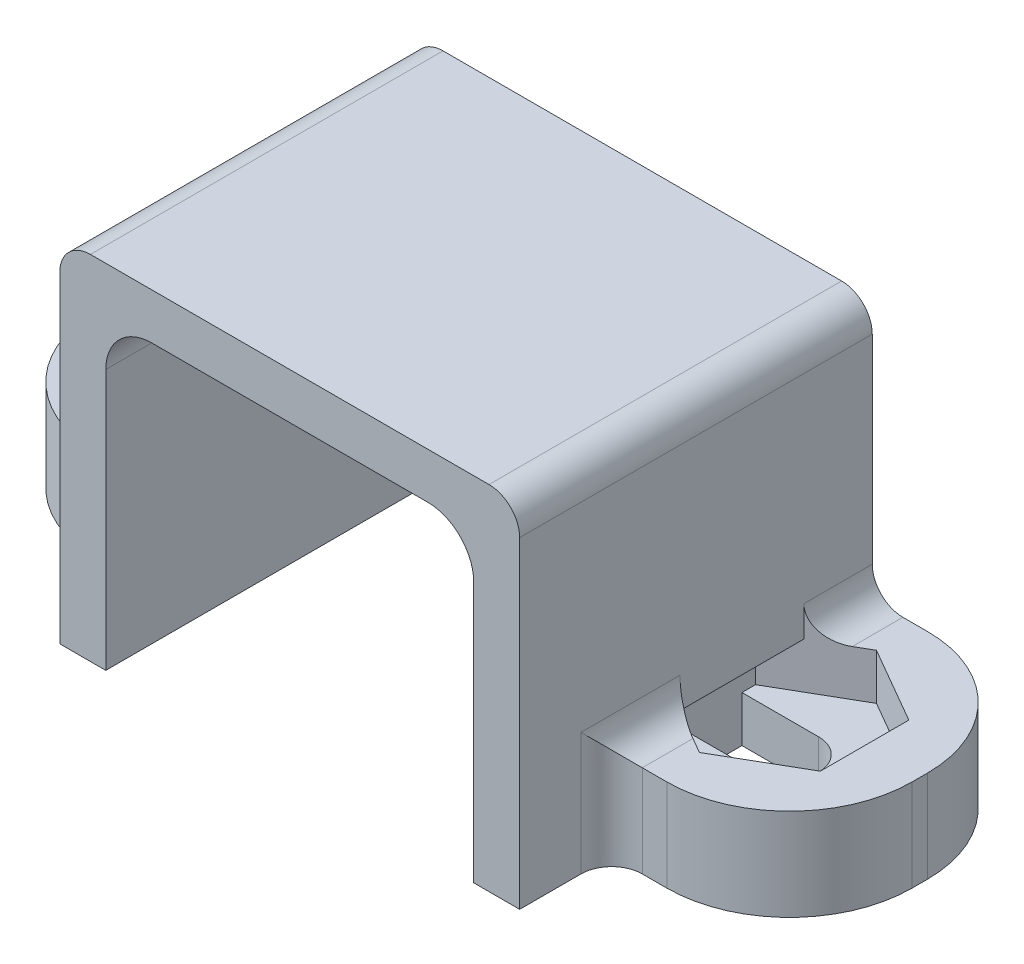
SolidWorks part; units mm, degrees
ref_plane "Front Plane" through (0, 0, 0) normal (0, 0, 1) x (1, 0, 0)
ref_plane "Top Plane" through (0, 0, 0) normal (0, 1, 0) x (1, 0, 0)
ref_plane "Right Plane" through (0, 0, 0) normal (1, 0, 0) x (0, 0, -1)
sketch "Sketch1" plane through (0, 0, 0) normal (0, 0, 1) x (1, 0, 0)
  line L0 (0, 0) -> (1.5, 0)
  line L1 (1.5, 0) -> (1.5, 10)
  line L2 (0, 0) -> (0, 10)
  line L3 (0, 10) -> (0, 11.5)
  line L4 (0, 11.5) -> (15, 11.5)
  line L5 (15, 11.5) -> (15, 0)
  line L6 (15, 0) -> (13.5, 0)
  line L7 (13.5, 0) -> (13.5, 10)
  line L8 (13.5, 10) -> (1.5, 10)
extrude "Boss-Extrude1" add sketch "Sketch1" along normal blind 17
sketch "Sketch12" plane through (0, 0, 0) normal (0, -1, 0) x (1, 0, 0)
  line L2 (15, 8) -> (0, 8)
  line L3 (15, 17) -> (15, 0) construction
  line L4 (0, 17) -> (0, 0) construction
split "Split2" trim tools "Sketch12" bodies to split 101 resulting bodies 116 117
combine bodies "Combine2" operation type add bodies to combine 116 117
sketch "Sketch13" plane through (0, 0, 0) normal (0, -1, 0) x (1, 0, 0)
  line L0 (7.5, 0) -> (7.5, 1.8013) construction
  line L1 (0, 0) -> (-5.8, 0)
  line L2 (0, 0) -> (0, 8.5)
  line L3 (0, 8.5) -> (-5.8, 8.5)
  line L4 (-5.8, 0) -> (-5.8, 8.5)
  line L5 (1.5, 0) -> (13.5, 0) construction
  line L6 (20.8, 0) -> (20.8, 8.5)
  line L7 (15, 8.5) -> (20.8, 8.5)
  line L8 (15, 0) -> (15, 8.5)
  line L9 (15, 0) -> (20.8, 0)
extrude "Boss-Extrude10" add sketch "Sketch13" against normal blind 3
fillet "Fillet7" radius 4 4 edges at (20.8, 1.5, 8.5) (20.8, 1.5, 0) (-5.8, 1.5, 0) (-5.8, 1.5, 8.5)
sketch "Sketch15" plane through (0, 0, 0) normal (-1, 0, 0) x (0, 0, 1)
  line L0 (0, 3) -> (17, 3)
  line L1 (17, 11.5) -> (17, 0) construction
split "Split3" trim tools "Sketch15" bodies to split 120 resulting bodies 121 122 123
sketch "Sketch16" plane through (0, 3, 0) normal (0, 1, 0) x (1, 0, 0)
  line L0 (1, -4.25) -> (-1.5, -4.25) construction
  line L2 (13.5, 0) -> (1.5, 0) construction
  line L3 (-1.5, -7.1368) -> (1, -5.6934)
  line L4 (1, -5.6934) -> (1, -2.8066)
  line L5 (1, -2.8066) -> (-1.5, -1.3632)
  line L6 (-1.5, -1.3632) -> (-4, -2.8066)
  line L7 (-4, -2.8066) -> (-4, -5.6934)
  line L8 (-4, -5.6934) -> (-1.5, -7.1368)
  line L9 (7.5, 0) -> (7.5, -2.8066) construction
  line L10 (7.5, -2.8066) -> (7.5, -4.25) construction
  line L11 (7.5, -4.25) -> (-1.5, -4.25) construction
  line L12 (-4, -2.8066) -> (-1.5, -1.3632)
  line L13 (-1.5, -7.1368) -> (-4, -5.6934)
  line L14 (1, -5.6934) -> (-1.5, -7.1368)
  line L15 (-1.5, -1.3632) -> (1, -2.8066)
  line L16 (14, -4.25) -> (16.5, -4.25) construction
  line L17 (16.5, -1.3632) -> (14, -2.8066)
  line L18 (14, -5.6934) -> (16.5, -7.1368)
  line L19 (16.5, -7.1368) -> (19, -5.6934)
  line L20 (19, -2.8066) -> (16.5, -1.3632)
  line L21 (19, -5.6934) -> (16.5, -7.1368)
  line L22 (19, -2.8066) -> (19, -5.6934)
  line L23 (16.5, -1.3632) -> (19, -2.8066)
  line L24 (14, -2.8066) -> (16.5, -1.3632)
  line L25 (14, -5.6934) -> (14, -2.8066)
  line L26 (16.5, -7.1368) -> (14, -5.6934)
extrude "Cut-Extrude1" cut sketch "Sketch16" against normal blind 1.5 contours L7 L8 L3 L4 L5 L6 | L25 L18 L19 L22 L20 L17 region at (-1.5, 3, 4.25) region at (16.5, 3, 4.25)
sketch "Sketch17" plane through (0, 1.5, 0) normal (0, 1, 0) x (1, 0, 0)
  line L0 (-1.5, -1.3632) -> (-1.5, -7.1368) construction
  line L3 (7.5, 0) -> (7.5, -1.3632) construction
  line L5 (16.5, -1.3632) -> (16.5, -7.1368) construction
  line L6 (16.5, -5.25) -> (14, -5.25)
  line L8 (16.5, -3.25) -> (14, -3.25)
  line L9 (14, -3.25) -> (14, -5.25)
  line L10 (1, -3.25) -> (1, -5.25)
  line L11 (-1.5, -3.25) -> (1, -3.25)
  line L12 (-1.5, -5.25) -> (1, -5.25)
  arc A0 (-1.5, -3.25) -> (-1.5, -5.25) centre (-1.5, -4.25) ccw
  arc A1 (16.5, -3.25) -> (16.5, -5.25) centre (16.5, -4.25) cw
extrude "Cut-Extrude2" cut sketch "Sketch17" against normal through all
combine bodies "Combine3" operation type add bodies to combine 123 128 127
fillet "Скругление1" radius 1 4 edges at (0, 3, 7.3854) (15, 3, 7.3854)
fillet "Скругление2" radius 1 4 edges at (0, 11.5, 8.5) (15, 11.5, 8.5)
fillet "Скругление3" radius 1.5 2 edges at (1.5, 10, 8.5) (13.5, 10, 8.5)
sketch "Эскиз1" plane through (0, 0, 0) normal (0, 0, 1) x (1, 0, 0)
  line L1 (-48.71, 32.1329) -> (27.0648, 32.1329)
  line L2 (-48.71, 32.1329) -> (-48.71, -4.2865)
  line L3 (-48.71, -4.2865) -> (27.0648, -4.2865)
  line L4 (27.0648, 32.1329) -> (27.0648, -4.2865)
  line L5 (-48.71, 32.1329) -> (27.0648, -4.2865) construction
  line L6 (-48.71, -4.2865) -> (27.0648, 32.1329) construction
  point P0 (-10.8226, 13.9232)
extrude "Вырез-Вытянуть1" cut sketch "Эскиз1" along normal blind 10 from offset 11.5
